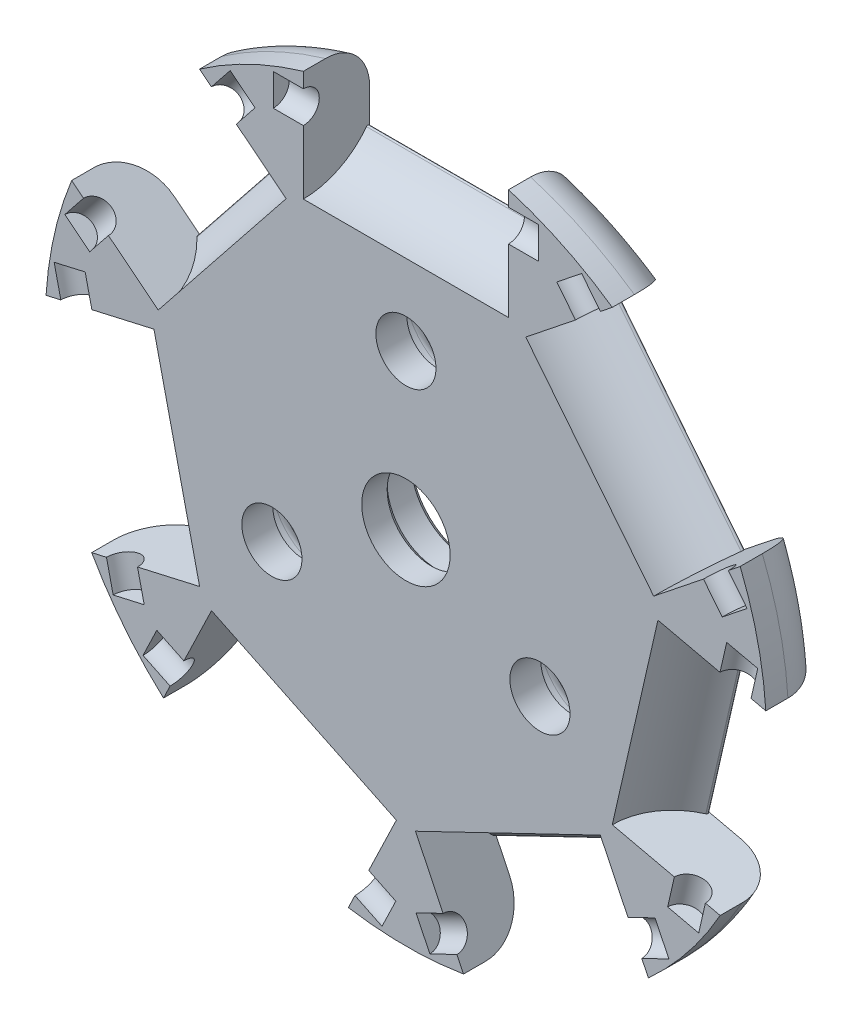
SolidWorks part; units mm, degrees
other "Markup1"
sketch "Sketch8" plane through (32.7336, 32.7336, 0) normal (0.5701, 0.1846, 0.8006) x (0.8043, 0.0736, -0.5897)
ref_plane "Front Plane" through (0, 0, 0) normal (0, 0, 1) x (1, 0, 0)
ref_plane "Top Plane" through (0, 0, 0) normal (0, 1, 0) x (1, 0, 0)
ref_plane "Right Plane" through (0, 0, 0) normal (1, 0, 0) x (0, 0, -1)
sketch "Sketch1" plane through (0, 0, 0) normal (0, 0, 1) x (1, 0, 0)
  circle A0 centre (0, 0) radius 25.8953
  dimension "D1" = 51.7906
extrude "Boss-Extrude2" add sketch "Sketch1" against normal blind 4.7625
fillet "Fillet1" radius 3.175 1 edges at (25.8953, 0, -4.7625)
sketch "Sketch2" plane through (0, 0, 0) normal (0, 0, 1) x (1, 0, 0)
  line L1 (-12.7, 25.8953) -> (12.7, 25.8953) construction
  line L2 (-7.366, 27.1653) -> (7.366, 27.1653)
  line L3 (-7.366, 27.1653) -> (-7.366, 16.7513)
  line L4 (-7.366, 16.7513) -> (7.366, 16.7513)
  line L5 (7.366, 27.1653) -> (7.366, 16.7513)
  line L6 (-7.366, 27.1653) -> (7.366, 16.7513) construction
  line L7 (-7.366, 16.7513) -> (7.366, 27.1653) construction
  line L35 (0, 0) -> (0, 25.8953) construction
  circle A1 centre (0, 0) radius 25.8953 construction
  point P10 (0, 21.9583)
  circle M7 centre (0, 0) radius 25.8953
  dimension "D1" = 14.732
  dimension "D2" = 10.414
  dimension "D3" = 1.27
  dimension "D4" = 25.4
extrude "Cut-Extrude2" cut sketch "Sketch2" against normal blind 12.7 contours L5 L3 L4 M7 | L3 L2 L5 L4 region at (0, 21.1523, 0)
pattern_circular "CirPattern1" count 7 over 360 about axis through (0, 0, 0) along (0, 0, 1) of "Cut-Extrude2"
ref_plane "Plane1" through (0, 0, 0) normal (1, 0, 0) x (0, 0, -1)
sketch "Sketch4" plane through (0, 0, 0) normal (1, 0, 0) x (0, 0, -1)
  line L0 (4.7625, 16.7513) -> (0, 16.7513) construction
  circle A0 centre (0, 22.5933) radius 1.143
  dimension "D1" = 2.286
  dimension "D2" = 5.842
extrude "Cut-Extrude4" cut sketch "Sketch4" against normal mid plane 19.05
pattern_circular "CirPattern2" count 7 over 360 about axis through (0, 0, 0) along (0, 0, 1) of "Cut-Extrude4"
sketch "Sketch5" plane through (0, 0, 0) normal (0, 0, 1) x (1, 0, 0)
  circle A0 centre (0, 0) radius 3.175
  dimension "D1" = 6.35
extrude "Cut-Extrude5" cut sketch "Sketch5" against normal through all
sketch "Sketch6" plane through (0, 0, -4.7625) normal (0, 0, -1) x (-1, 0, 0)
  circle A4 centre (0, 11.1125) radius 2.159
  circle A5 centre (9.6237, -5.5562) radius 2.159
  circle A6 centre (-9.6237, -5.5563) radius 2.159
  point P3 (-11.0087, -8.0361)
  point P4 (0, 0)
  point P9 (0, 0)
  dimension "D1" = 4.318
  dimension "D2" = 11.1125
extrude "Cut-Extrude7" cut sketch "Sketch6" against normal through all
sketch "Sketch7" plane through (0, 0, -4.7625) normal (0, 0, -1) x (-1, 0, 0)
  circle A2 centre (-9.6237, -5.5563) radius 4.064
  circle A3 centre (0, 11.1125) radius 4.064
  circle A4 centre (9.6237, -5.5562) radius 4.064
  dimension "D1" = 8.128
extrude "Cut-Extrude8" cut sketch "Sketch7" against normal blind 2.54
sketch "Sketch10" plane through (7.366, 0, 0) normal (-1, 0, 0) x (0, 0, 1)
  line L0 (-4.7625, 21.4931) -> (-4.7625, 16.7513) construction
  line L1 (-4.7625, 16.7513) -> (0, 16.7513)
  line L2 (-4.7625, 16.7513) -> (-4.7625, 19.4342)
  line L4 (0, 16.7513) -> (0, 16.8783)
  arc A0 (-4.7625, 19.4342) -> (0, 16.8783) centre (0, 22.5933) ccw
  dimension "D1" = 11.43
  dimension "D2" = 4.7625
extrude "Boss-Extrude4" add sketch "Sketch10" along normal up to next
fillet "Fillet2" radius 0.127 1 edges at (0, 19.4342, -4.7625)
pattern_circular "CirPattern5" count 7 over 360 about axis through (0, 0, 0) along (0, 0, 1) of "Boss-Extrude4", "Fillet2"
sketch "Sketch11" plane through (0, 0, -4.7625) normal (0, 0, -1) x (-1, 0, 0)
  circle A0 centre (0, 0) radius 4.0005
  dimension "D1" = 8.001
extrude "Cut-Extrude9" cut sketch "Sketch11" against normal blind 2.54
chamfer "Chamfer1" distance 0.3969 angle 45 2 edges at (-4.0005, 0, -4.7625) (-3.175, 0, -2.2225)
fillet "Fillet3" radius 0.7937 3 edges at (-13.6877, -5.5562, -4.7625) (5.5597, -5.5563, -4.7625) (-4.064, 11.1125, -4.7625)
